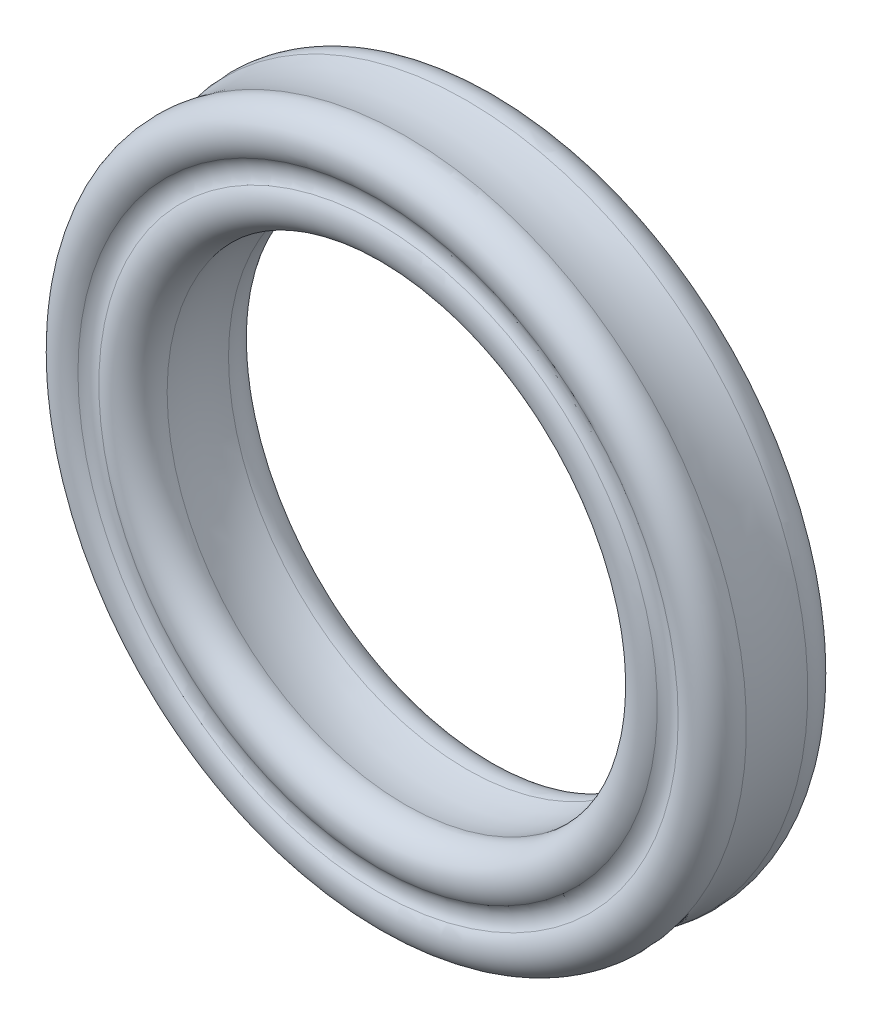
SolidWorks part; units mm, degrees
ref_plane "Plan1" through (0, 0, 0) normal (0, 0, 1) x (1, 0, 0)
ref_plane "Plan2" through (0, 0, 0) normal (0, 1, 0) x (1, 0, 0)
ref_plane "Plan3" through (0, 0, 0) normal (1, 0, 0) x (0, 0, -1)
sketch "Esquisse1" plane through (0, 0, 0) normal (1, 0, 0) x (0, 0, -1)
  line L0 (0, 0) -> (2.9, 0) construction
  line L1 (1.45, 7.85) -> (1.45, 5.45) construction
  line L2 (0, 7.85) -> (2.9, 7.85) construction
  line L3 (0, 7.85) -> (0, 5.45) construction
  line L4 (0, 5.45) -> (2.9, 5.45) construction
  line L5 (2.9, 7.85) -> (2.9, 5.45) construction
  line L6 (2.9, 6.65) -> (0, 6.65) construction
  arc A0 (0.7457, 7.832) -> (0.12, 6.89) centre (0.6, 7.25) ccw
  arc A1 (0.7457, 5.468) -> (0.12, 6.41) centre (0.6, 6.05) cw
  arc A2 (0.12, 6.41) -> (0.12, 6.89) centre (-0.2, 6.65) ccw
  arc A3 (2.1543, 5.468) -> (2.78, 6.41) centre (2.3, 6.05) ccw
  arc A4 (2.78, 6.41) -> (2.78, 6.89) centre (3.1, 6.65) cw
  arc A5 (2.1543, 7.832) -> (2.78, 6.89) centre (2.3, 7.25) cw
  arc A6 (0.7457, 7.832) -> (2.1543, 7.832) centre (1.45, 10.6452) ccw
  arc A7 (0.7457, 5.468) -> (2.1543, 5.468) centre (1.45, 2.6548) cw
  point P18 (0.6, 6.65)
  dimension "D4" = 1.2
  dimension "D5" = 0.4
  dimension "D6" = 2.9
  dimension "E" = 2.4
  dimension "F" = 2.9
  dimension "De" = 7.85
revolve "Base-Révolution" add sketch "Esquisse1" angle 360 about L0
ref_axis "Axe1" through (0, 0, -50) along (0, 0, 1)
equation "\"D4@Esquisse1\"=\"E@Esquisse1\"/2"
equation "\"D5@Esquisse1\"=\"D4@Esquisse1\"/3"
equation "\"D6@Esquisse1\"=\"F@Esquisse1\""
